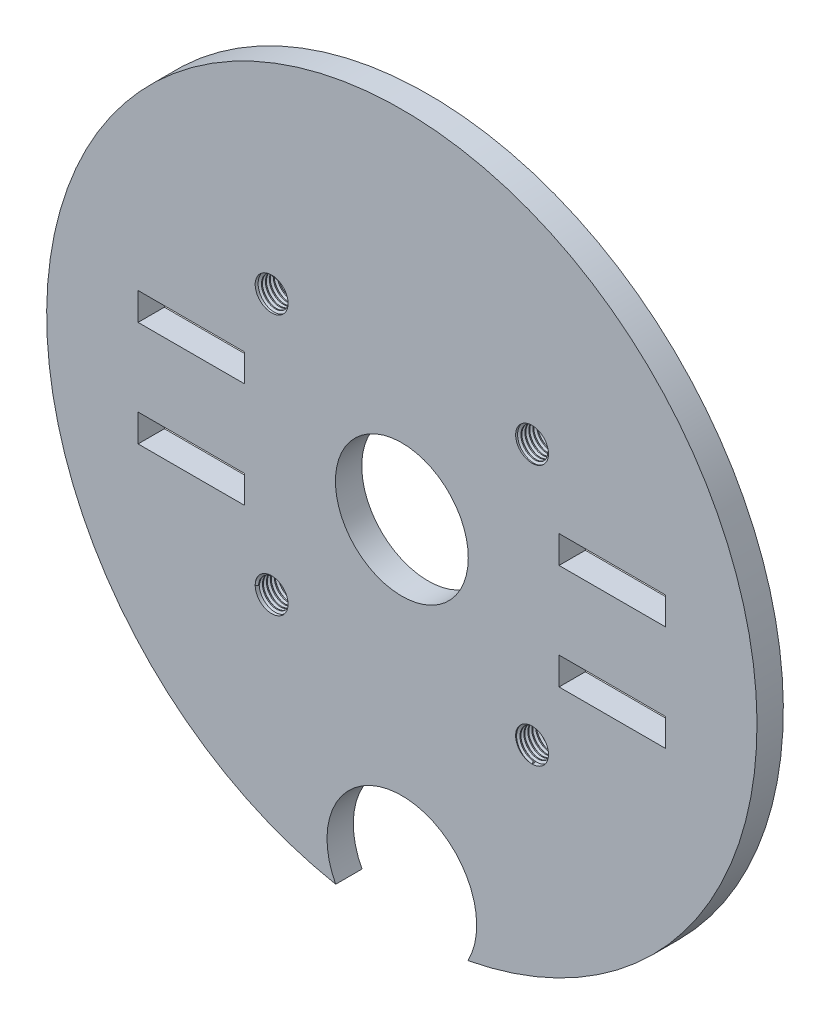
SolidWorks part; units mm, degrees
ref_plane "前视基准面" through (0, 0, 0) normal (0, 0, 1) x (1, 0, 0)
ref_plane "上视基准面" through (0, 0, 0) normal (0, 1, 0) x (1, 0, 0)
ref_plane "右视基准面" through (0, 0, 0) normal (1, 0, 0) x (0, 0, -1)
other "质心 (COM)"
sketch "草图1" plane through (0, 0, 0) normal (0, 0, 1) x (1, 0, 0)
  line L0 (0, 0) -> (0, -27) construction
  line L1 (0, 0) -> (-16.3098, -16.3098) construction
  line L2 (20.05, -5.05) -> (20.05, -2.95)
  line L3 (11.95, -2.95) -> (20.05, -2.95)
  line L4 (11.95, -5.05) -> (11.95, -2.95)
  line L5 (11.95, -5.05) -> (20.05, -5.05)
  line L6 (0, 0) -> (11.95, -2.95) construction
  line L7 (0, 0) -> (27, 0) construction
  line L8 (11.95, 5.05) -> (11.95, 2.95)
  line L9 (20.05, 5.05) -> (20.05, 2.95)
  line L10 (11.95, 5.05) -> (20.05, 5.05)
  line L11 (11.95, 2.95) -> (20.05, 2.95)
  line L12 (-11.95, 5.05) -> (-11.95, 2.95)
  line L13 (-20.05, 5.05) -> (-20.05, 2.95)
  line L14 (-11.95, 5.05) -> (-20.05, 5.05)
  line L15 (-11.95, 2.95) -> (-20.05, 2.95)
  line L16 (-11.95, -5.05) -> (-11.95, -2.95)
  line L17 (-20.05, -5.05) -> (-20.05, -2.95)
  line L18 (-11.95, -2.95) -> (-20.05, -2.95)
  line L19 (-11.95, -5.05) -> (-20.05, -5.05)
  circle A0 centre (0, 0) radius 5.05
  circle A1 centre (0, 0) radius 27 construction
  circle A2 centre (0, 0) radius 14 construction
  circle A3 centre (-9.8995, -9.8995) radius 1.25
  circle A4 centre (-9.8995, 9.8995) radius 1.25
  circle A5 centre (9.8995, 9.8995) radius 1.25
  circle A6 centre (9.8995, -9.8995) radius 1.25
  arc A9 (-5.0274, -26.5278) -> (5.0274, -26.5278) centre (0, 0) cw
  circle A10 centre (0, 0) radius 12 construction
  arc A11 (-5.0274, -26.5278) -> (5.0274, -26.5278) centre (0, -23.8649) cw
  point P26 (11.95, -4)
  dimension "D1" = 10.1
  dimension "D2" = 54
  dimension "D4" = 28
  dimension "D5" = 4
  dimension "D6" = 24
  dimension "D7" = 2.5
  dimension "D3" = 45
extrude "凸台-拉伸1" add sketch "草图1" along normal blind 2
thread "螺纹线2" pitch 0.3 method extrude profile "螺纹线轮廓3" start angle 0, offset 0, length 2, pitch 0.3, diameter 2.5
ref_plane "基准面3" through (-11.1495, -9.8995, 2) normal (0, -1, 0) x (-1, 0, 0)
sketch "螺纹线轮廓3" plane through (-11.1495, -9.8995, 2) normal (0, -1, 0) x (-1, 0, 0)
  line L0 (0, 0) -> (0, 0.3) construction
  line L11 (0, 0) -> (0, 0.2625)
  line L12 (0, 0.2625) -> (-0.1624, 0.1687)
  line L13 (-0.1624, 0.1687) -> (-0.1624, 0.0937)
  line L15 (-0.1624, 0.0937) -> (0, 0)
  line L17 (-0.1624, 0.1312) -> (0, 0.1312) construction
  point P2 (0, 0)
  dimension "Pitch" = 0.3
  dimension "Profile_Angle" = 60
  dimension "Profile_Land" = 0.075
  dimension "Profile_Height" = 0.1624
pattern_circular "阵列(圆周)1" count 4 over 360 about axis through (0, 0, 2) along (0, 0, -1) of "螺纹线2" reverse direction yes
sketch "草图10" plane through (0, 0, 0) normal (0, 0, -1) x (-1, 0, 0)
  circle A0 centre (0, 0) radius 27
extrude "切除-拉伸1" cut sketch "草图10" along normal blind 10
